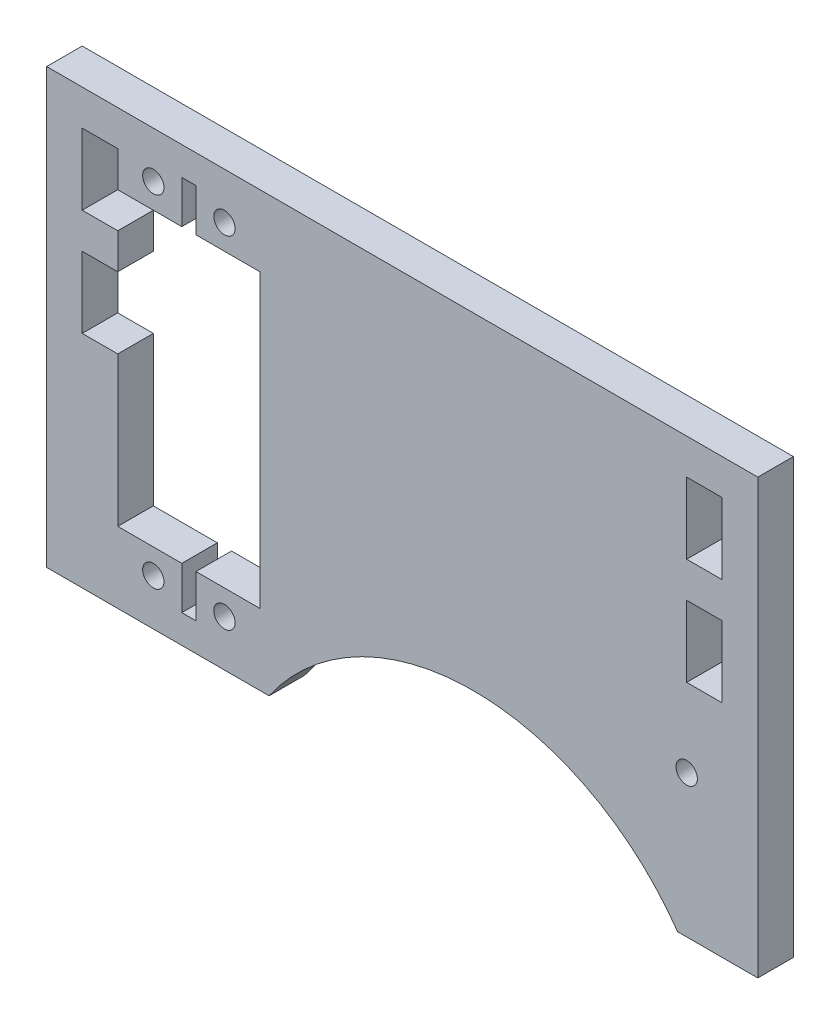
SolidWorks part; units mm, degrees
ref_plane "Plan de face" through (0, 0, 0) normal (0, 0, 1) x (1, 0, 0)
ref_plane "Plan de dessus" through (0, 0, 0) normal (0, 1, 0) x (1, 0, 0)
ref_plane "Plan de droite" through (0, 0, 0) normal (1, 0, 0) x (0, 0, -1)
sketch "Esquisse1" plane through (0, 0, 0) normal (0, 0, 1) x (1, 0, 0)
  line L0 (20, 71) -> (20, 0) construction
  line L1 (0, 0) -> (31.2772, 0)
  line L2 (0, 0) -> (0, 61)
  line L3 (0, 61) -> (100, 61)
  line L4 (100, 0) -> (100, 61)
  line L5 (10, 30.5) -> (30, 30.5) construction
  line L6 (10, 51) -> (19, 51)
  line L7 (10, 46) -> (10, 41)
  line L8 (10, 10) -> (19, 10)
  line L9 (30, 51) -> (30, 10)
  line L10 (20, 20) -> (90, 20) construction
  line L11 (88.7228, 0) -> (100, 0)
  line L12 (21, 4) -> (21, 10)
  line L13 (19, 57) -> (21, 57)
  line L14 (19, 57) -> (19, 51)
  line L15 (21, 10) -> (30, 10)
  line L16 (21, 57) -> (21, 51)
  line L17 (19, 4) -> (21, 4)
  line L18 (19, 4) -> (19, 10)
  line L19 (21, 51) -> (30, 51)
  line L20 (10, 31) -> (10, 10)
  line L21 (90, 56) -> (95, 56)
  line L22 (90, 56) -> (90, 46)
  line L23 (90, 46) -> (95, 46)
  line L24 (95, 56) -> (95, 46)
  line L25 (90, 41) -> (95, 41)
  line L26 (90, 41) -> (90, 31)
  line L27 (90, 31) -> (95, 31)
  line L28 (95, 41) -> (95, 31)
  line L29 (5, 56) -> (10, 56)
  line L30 (5, 56) -> (5, 46)
  line L31 (5, 46) -> (10, 46)
  line L32 (10, 56) -> (10, 51)
  line L33 (5, 41) -> (10, 41)
  line L34 (5, 41) -> (5, 31)
  line L35 (5, 31) -> (10, 31)
  circle A0 centre (15, 6.5) radius 1.5
  circle A1 centre (25, 6.5) radius 1.5
  circle A2 centre (25, 54.5) radius 1.5
  circle A3 centre (15, 54.5) radius 1.5
  circle A4 centre (20, 20) radius 1.5 construction
  circle A5 centre (20, 20) radius 1.5 construction
  circle A6 centre (90, 20) radius 1.5
  circle A7 centre (60, -20) radius 35 construction
  arc A8 (31.2772, 0) -> (88.7228, 0) centre (60, -20) cw
  dimension "D6" = 3.5
  dimension "D8" = 3
  dimension "D9" = 3
  dimension "D10" = 70
  dimension "D13" = 70
  dimension "D16" = 2
  dimension "D1" = 10
  dimension "D2" = 41
  dimension "D3" = 20
  dimension "D4" = 10
  dimension "D5" = 100
  dimension "D7" = 5
  dimension "D11" = 10
  dimension "D12" = 10
  dimension "D14" = 40
  dimension "D15" = 40
  dimension "D17" = 6
  dimension "D18" = 5
  dimension "D19" = 5
  dimension "D20" = 10
  dimension "D21" = 5
  dimension "D22" = 5
  dimension "D23" = 5
  dimension "D24" = 10
extrude "Boss.-Extru.1" add sketch "Esquisse1" along normal blind 5
